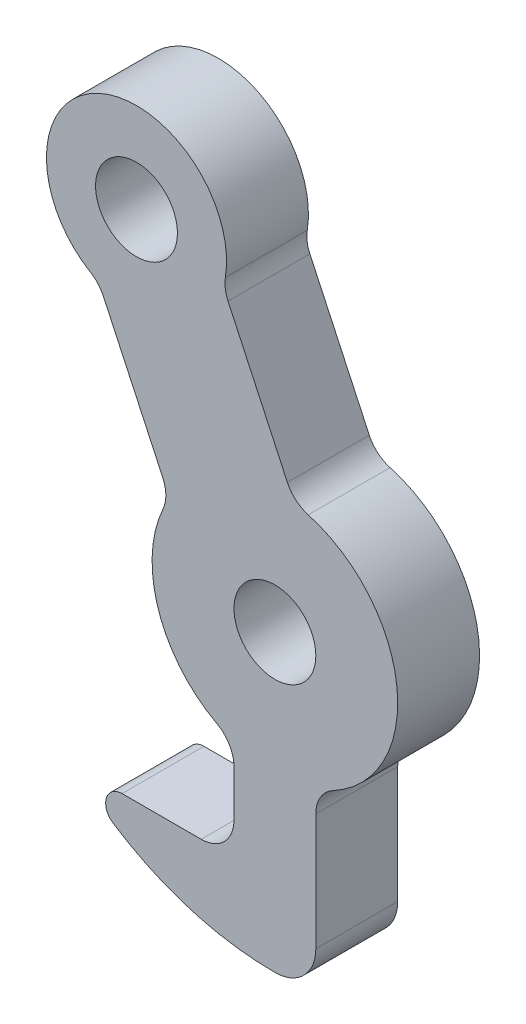
SolidWorks part; units mm, degrees
ref_plane "Front Plane" through (0, 0, 0) normal (0, 0, 1) x (1, 0, 0)
ref_plane "Top Plane" through (0, 0, 0) normal (0, 1, 0) x (1, 0, 0)
ref_plane "Right Plane" through (0, 0, 0) normal (1, 0, 0) x (0, 0, -1)
sketch "Sketch1" plane through (0, 0, 0) normal (0, 0, 1) x (1, 0, 0)
  line L0 (1.4992, 9.4063) -> (-3.9943, 21.1872)
  line L1 (-8.1693, 4.8978) -> (-13.6628, 16.6787)
  line L3 (3.175, -8.9803) -> (3.175, -19.685)
  line L4 (0, 0) -> (-10.7345, 23.0202) construction
  line L7 (0, -19.685) -> (0, 0) construction
  line L9 (-3.175, -8.9803) -> (-3.175, -16.7736)
  line L11 (-12.9813, -16.7736) -> (-15.5314, -16.7736) construction
  line L12 (-3.175, -16.7736) -> (-15.5314, -16.7736)
  arc A0 (3.175, -8.9803) -> (1.4992, 9.4063) centre (0, 0) ccw
  circle A1 centre (-10.7345, 23.0202) radius 3.175
  arc A2 (0, -22.86) -> (3.175, -19.685) centre (0, -19.685) ccw
  arc A3 (-3.9943, 21.1872) -> (-13.6628, 16.6787) centre (-10.7345, 23.0202) ccw
  circle A4 centre (0, 0) radius 3.175
  arc A6 (-8.1693, 4.8978) -> (-3.175, -8.9803) centre (0, 0) ccw
  arc A7 (0, -22.86) -> (-15.5314, -16.7736) centre (0, 0) cw
  point P16 (0, 0)
  point P17 (-14.3911, -17.7617)
  point P21 (0, 0)
  dimension "D1" = 6.35
  dimension "D3" = 6.35
  dimension "D4" = 19.05
  dimension "D5" = 13.97
  dimension "D7" = 22.86
  dimension "D2" = 6.35
  dimension "D6" = 10.668
  dimension "D8" = 25.4
extrude "Boss-Extrude1" add sketch "Sketch1" along normal mid plane 6.35
fillet "Fillet1" radius 2.54 7 edges at (-3.9943, 21.1872, 0) (-13.6628, 16.6787, 0) (-8.1693, 4.8978, 0) (1.4992, 9.4063, 0) (3.175, -8.9803, 0) (-3.175, -8.9803, 0) (-3.175, -16.7736, 0)
fillet "Fillet2" radius 1.27 1 edges at (-15.5314, -16.7736, 0)
